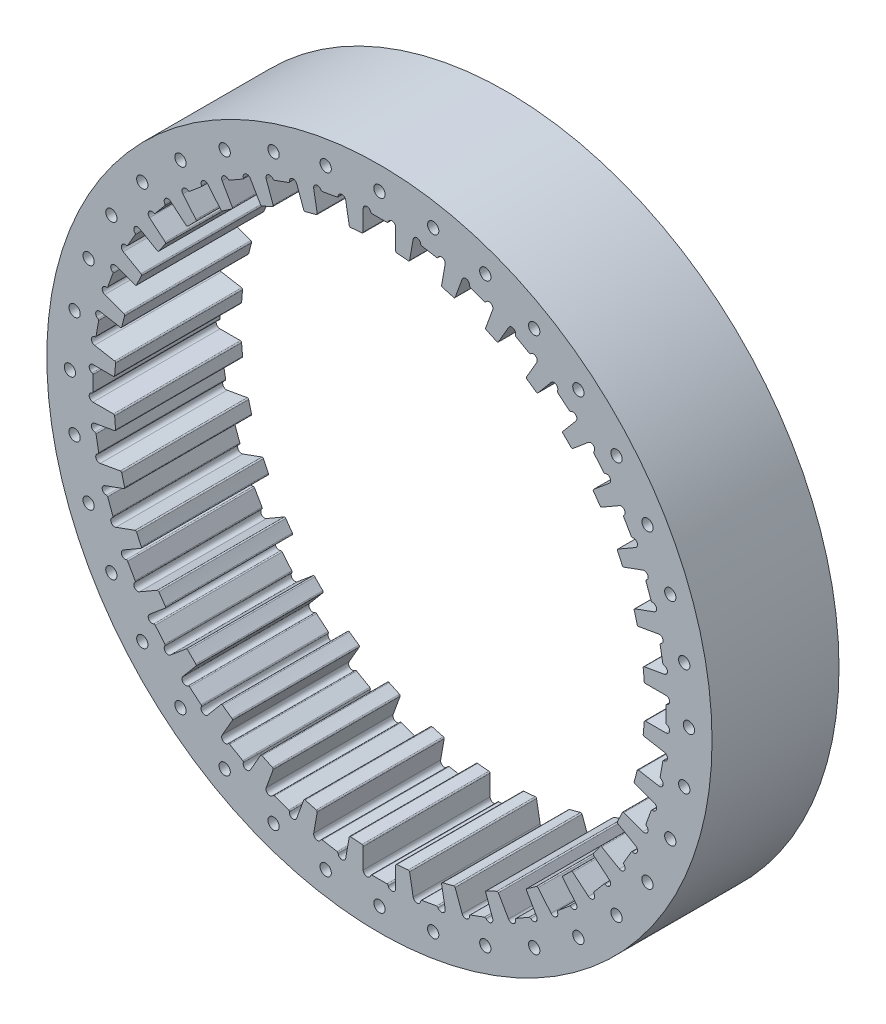
SolidWorks part; units mm, degrees
material "ABS"
ref_plane "Front Plane" through (0, 0, 0) normal (0, 0, 1) x (1, 0, 0)
ref_plane "Top Plane" through (0, 0, 0) normal (0, 1, 0) x (1, 0, 0)
ref_plane "Right Plane" through (0, 0, 0) normal (1, 0, 0) x (0, 0, -1)
ref_axis "Axis1" through (0, 0, -101.69) along (0, 0, 1)
sketch "Sketch1" plane through (0, 0, 0) normal (0, 0, 1) x (1, 0, 0)
  line L0 (0, 0) -> (50000, 0) construction
  line L1 (0, 0) -> (0, 50000) construction
  circle A0 centre (0, 0) radius 66.548
  circle A1 centre (0, 0) radius 53.086
  dimension "D1" = 133.096
  dimension "D2" = 106.172
extrude "Boss-Extrude1" add sketch "Sketch1" against normal blind 25.4
sketch "Sketch2" plane through (0, 0, 0) normal (0, 0, 1) x (1, 0, 0)
  line L0 (0, 0) -> (50000, 0) construction
  line L1 (0, 0) -> (0, 50000) construction
  circle A0 centre (0, 61.9252) radius 1.1303
  dimension "D1" = 2.2606
  dimension "D2" = 61.9252
extrude "Cut-Extrude1" cut sketch "Sketch2" against normal up to surface (25.4 mm away) up to face at (53.086, 0, -25.4)
pattern_circular "CirPattern1" count 36 over 360 about axis through (0, 0, -101.69) along (0, 0, 1) of "Cut-Extrude1"
sketch "Sketch3" plane through (0, 0, 0) normal (0, 0, 1) x (1, 0, 0)
  line L0 (0, 0) -> (50000, 0) construction
  line L1 (0, 0) -> (0, 50000) construction
  line L2 (57.3024, 1.5055) -> (57.3024, -1.5055)
  line L3 (57.3024, -3.2512) -> (53.2247, -3.2512)
  line L4 (57.3024, 3.2512) -> (53.2247, 3.2512)
  circle A0 centre (0, 0) radius 53.086 construction
  circle A2 centre (0, 0) radius 53.086 construction
  arc A3 (57.3024, -1.5055) -> (57.4929, -1.7514) centre (57.5564, -1.5055) ccw
  arc A4 (57.4929, -1.7514) -> (57.3024, -3.2512) centre (57.3024, -2.4892) cw
  arc A5 (53.2247, -3.2512) -> (52.9713, -3.4885) centre (53.2247, -3.5052) ccw
  arc A6 (53.2247, 3.2512) -> (52.9713, 3.4885) centre (53.2247, 3.5052) cw
  arc A7 (57.4929, 1.7514) -> (57.3024, 3.2512) centre (57.3024, 2.4892) ccw
  arc A8 (57.3024, 1.5055) -> (57.4929, 1.7514) centre (57.5564, 1.5055) cw
  arc A9 (52.9713, 3.4885) -> (52.9713, -3.4885) centre (0, 0) cw
  point P27 (57.3024, 0)
  dimension "D1" = 0.254
  dimension "D2" = 0.762
  dimension "D3" = 57.3024
  dimension "D4" = 3.2512
extrude "Cut-Extrude2" cut sketch "Sketch3" against normal blind 25.4 contours A6 A9 A5 L3 A4 A3 L2 A8 A7 L4 region at (55.3285, 0, 0)
pattern_circular "CirPattern2" count 36 over 360 about axis through (0, 0, -101.69) along (0, 0, 1) of "Cut-Extrude2"
sketch "Sketch4" plane through (0, 0, 0) normal (0, 0, 1) x (1, 0, 0)
  line L0 (0, 0) -> (-50000, 0) construction
  line L1 (0, 0) -> (0, 50000) construction
  line L2 (-1.5055, 57.3024) -> (1.5055, 57.3024) construction
  line L3 (-2.921, 57.3024) -> (2.921, 57.3024)
  line L4 (-3.175, 57.0484) -> (-3.175, 51.2064)
  line L5 (-2.921, 50.9524) -> (2.921, 50.9524)
  line L6 (3.175, 57.0484) -> (3.175, 51.2064)
  line L7 (7.0738, 56.9391) -> (12.8271, 55.9246)
  line L8 (6.7796, 56.733) -> (5.7651, 50.9798)
  line L9 (5.9712, 50.6855) -> (11.7244, 49.6711)
  line L10 (13.0331, 55.6304) -> (12.0187, 49.8771)
  line L11 (16.8537, 54.8457) -> (22.3434, 52.8476)
  line L12 (16.5282, 54.6939) -> (14.5301, 49.2042)
  line L13 (14.6819, 48.8786) -> (20.1716, 46.8806)
  line L14 (22.4952, 52.522) -> (20.4971, 47.0324)
  line L15 (26.1215, 51.0858) -> (31.1809, 48.1648)
  line L16 (25.7746, 50.9929) -> (22.8536, 45.9335)
  line L17 (22.9465, 45.5866) -> (28.0059, 42.6656)
  line L18 (31.2738, 47.8179) -> (28.3528, 42.7585)
  line L19 (34.5957, 45.7738) -> (39.0709, 42.0186)
  line L20 (34.2378, 45.7425) -> (30.4826, 41.2672)
  line L21 (30.514, 40.9094) -> (34.9892, 37.1542)
  line L22 (39.1022, 41.6608) -> (35.347, 37.1855)
  line L23 (42.0186, 39.0709) -> (45.7738, 34.5957)
  line L24 (41.6608, 39.1022) -> (37.1855, 35.347)
  line L25 (37.1542, 34.9892) -> (40.9094, 30.514)
  line L26 (45.7425, 34.2378) -> (41.2672, 30.4826)
  line L27 (48.1648, 31.1809) -> (51.0858, 26.1215)
  line L28 (47.8179, 31.2738) -> (42.7585, 28.3528)
  line L29 (42.6656, 28.0059) -> (45.5866, 22.9465)
  line L30 (50.9929, 25.7746) -> (45.9335, 22.8536)
  line L31 (52.8476, 22.3434) -> (54.8457, 16.8537)
  line L32 (52.522, 22.4952) -> (47.0324, 20.4971)
  line L33 (46.8806, 20.1716) -> (48.8786, 14.6819)
  line L34 (54.6939, 16.5282) -> (49.2042, 14.5301)
  line L35 (55.9246, 12.8271) -> (56.9391, 7.0738)
  line L36 (55.6304, 13.0331) -> (49.8771, 12.0187)
  line L37 (49.6711, 11.7244) -> (50.6855, 5.9712)
  line L38 (56.733, 6.7796) -> (50.9798, 5.7651)
  line L39 (57.3024, 2.921) -> (57.3024, -2.921)
  line L40 (57.0484, 3.175) -> (51.2064, 3.175)
  line L41 (50.9524, 2.921) -> (50.9524, -2.921)
  line L42 (57.0484, -3.175) -> (51.2064, -3.175)
  line L43 (56.9391, -7.0738) -> (55.9246, -12.8271)
  line L44 (56.733, -6.7796) -> (50.9798, -5.7651)
  line L45 (50.6855, -5.9712) -> (49.6711, -11.7244)
  line L46 (55.6304, -13.0331) -> (49.8771, -12.0187)
  line L47 (54.8457, -16.8537) -> (52.8476, -22.3434)
  line L48 (54.6939, -16.5282) -> (49.2042, -14.5301)
  line L49 (48.8786, -14.6819) -> (46.8806, -20.1716)
  line L50 (52.522, -22.4952) -> (47.0324, -20.4971)
  line L51 (51.0858, -26.1215) -> (48.1648, -31.1809)
  line L52 (50.9929, -25.7746) -> (45.9335, -22.8536)
  line L53 (45.5866, -22.9465) -> (42.6656, -28.0059)
  line L54 (47.8179, -31.2738) -> (42.7585, -28.3528)
  line L55 (45.7738, -34.5957) -> (42.0186, -39.0709)
  line L56 (45.7425, -34.2378) -> (41.2672, -30.4826)
  line L57 (40.9094, -30.514) -> (37.1542, -34.9892)
  line L58 (41.6608, -39.1022) -> (37.1855, -35.347)
  line L59 (39.0709, -42.0186) -> (34.5957, -45.7738)
  line L60 (39.1022, -41.6608) -> (35.347, -37.1855)
  line L61 (34.9892, -37.1542) -> (30.514, -40.9094)
  line L62 (34.2378, -45.7425) -> (30.4826, -41.2672)
  line L63 (31.1809, -48.1648) -> (26.1215, -51.0858)
  line L64 (31.2738, -47.8179) -> (28.3528, -42.7585)
  line L65 (28.0059, -42.6656) -> (22.9465, -45.5866)
  line L66 (25.7746, -50.9929) -> (22.8536, -45.9335)
  line L67 (22.3434, -52.8476) -> (16.8537, -54.8457)
  line L68 (22.4952, -52.522) -> (20.4971, -47.0324)
  line L69 (20.1716, -46.8806) -> (14.6819, -48.8786)
  line L70 (16.5282, -54.6939) -> (14.5301, -49.2042)
  line L71 (12.8271, -55.9246) -> (7.0738, -56.9391)
  line L72 (13.0331, -55.6304) -> (12.0187, -49.8771)
  line L73 (11.7244, -49.6711) -> (5.9712, -50.6855)
  line L74 (6.7796, -56.733) -> (5.7651, -50.9798)
  line L75 (2.921, -57.3024) -> (-2.921, -57.3024)
  line L76 (3.175, -57.0484) -> (3.175, -51.2064)
  line L77 (2.921, -50.9524) -> (-2.921, -50.9524)
  line L78 (-3.175, -57.0484) -> (-3.175, -51.2064)
  line L79 (-7.0738, -56.9391) -> (-12.8271, -55.9246)
  line L80 (-6.7796, -56.733) -> (-5.7651, -50.9798)
  line L81 (-5.9712, -50.6855) -> (-11.7244, -49.6711)
  line L82 (-13.0331, -55.6304) -> (-12.0187, -49.8771)
  line L83 (-16.8537, -54.8457) -> (-22.3434, -52.8476)
  line L84 (-16.5282, -54.6939) -> (-14.5301, -49.2042)
  line L85 (-14.6819, -48.8786) -> (-20.1716, -46.8806)
  line L86 (-22.4952, -52.522) -> (-20.4971, -47.0324)
  line L87 (-26.1215, -51.0858) -> (-31.1809, -48.1648)
  line L88 (-25.7746, -50.9929) -> (-22.8536, -45.9335)
  line L89 (-22.9465, -45.5866) -> (-28.0059, -42.6656)
  line L90 (-31.2738, -47.8179) -> (-28.3528, -42.7585)
  line L91 (-34.5957, -45.7738) -> (-39.0709, -42.0186)
  line L92 (-34.2378, -45.7425) -> (-30.4826, -41.2672)
  line L93 (-30.514, -40.9094) -> (-34.9892, -37.1542)
  line L94 (-39.1022, -41.6608) -> (-35.347, -37.1855)
  line L95 (-42.0186, -39.0709) -> (-45.7738, -34.5957)
  line L96 (-41.6608, -39.1022) -> (-37.1855, -35.347)
  line L97 (-37.1542, -34.9892) -> (-40.9094, -30.514)
  line L98 (-45.7425, -34.2378) -> (-41.2672, -30.4826)
  line L99 (-48.1648, -31.1809) -> (-51.0858, -26.1215)
  line L100 (-47.8179, -31.2738) -> (-42.7585, -28.3528)
  line L101 (-42.6656, -28.0059) -> (-45.5866, -22.9465)
  line L102 (-50.9929, -25.7746) -> (-45.9335, -22.8536)
  line L103 (-52.8476, -22.3434) -> (-54.8457, -16.8537)
  line L104 (-52.522, -22.4952) -> (-47.0324, -20.4971)
  line L105 (-46.8806, -20.1716) -> (-48.8786, -14.6819)
  line L106 (-54.6939, -16.5282) -> (-49.2042, -14.5301)
  line L107 (-55.9246, -12.8271) -> (-56.9391, -7.0738)
  line L108 (-55.6304, -13.0331) -> (-49.8771, -12.0187)
  line L109 (-49.6711, -11.7244) -> (-50.6855, -5.9712)
  line L110 (-56.733, -6.7796) -> (-50.9798, -5.7651)
  line L111 (-57.3024, -2.921) -> (-57.3024, 2.921)
  line L112 (-57.0484, -3.175) -> (-51.2064, -3.175)
  line L113 (-50.9524, -2.921) -> (-50.9524, 2.921)
  line L114 (-57.0484, 3.175) -> (-51.2064, 3.175)
  line L115 (-56.9391, 7.0738) -> (-55.9246, 12.8271)
  line L116 (-56.733, 6.7796) -> (-50.9798, 5.7651)
  line L117 (-50.6855, 5.9712) -> (-49.6711, 11.7244)
  line L118 (-55.6304, 13.0331) -> (-49.8771, 12.0187)
  line L119 (-54.8457, 16.8537) -> (-52.8476, 22.3434)
  line L120 (-54.6939, 16.5282) -> (-49.2042, 14.5301)
  line L121 (-48.8786, 14.6819) -> (-46.8806, 20.1716)
  line L122 (-52.522, 22.4952) -> (-47.0324, 20.4971)
  line L123 (-51.0858, 26.1215) -> (-48.1648, 31.1809)
  line L124 (-50.9929, 25.7746) -> (-45.9335, 22.8536)
  line L125 (-45.5866, 22.9465) -> (-42.6656, 28.0059)
  line L126 (-47.8179, 31.2738) -> (-42.7585, 28.3528)
  line L127 (-45.7738, 34.5957) -> (-42.0186, 39.0709)
  line L128 (-45.7425, 34.2378) -> (-41.2672, 30.4826)
  line L129 (-40.9094, 30.514) -> (-37.1542, 34.9892)
  line L130 (-41.6608, 39.1022) -> (-37.1855, 35.347)
  line L131 (-39.0709, 42.0186) -> (-34.5957, 45.7738)
  line L132 (-39.1022, 41.6608) -> (-35.347, 37.1855)
  line L133 (-34.9892, 37.1542) -> (-30.514, 40.9094)
  line L134 (-34.2378, 45.7425) -> (-30.4826, 41.2672)
  line L135 (-31.1809, 48.1648) -> (-26.1215, 51.0858)
  line L136 (-31.2738, 47.8179) -> (-28.3528, 42.7585)
  line L137 (-28.0059, 42.6656) -> (-22.9465, 45.5866)
  line L138 (-25.7746, 50.9929) -> (-22.8536, 45.9335)
  line L139 (-22.3434, 52.8476) -> (-16.8537, 54.8457)
  line L140 (-22.4952, 52.522) -> (-20.4971, 47.0324)
  line L141 (-20.1716, 46.8806) -> (-14.6819, 48.8786)
  line L142 (-16.5282, 54.6939) -> (-14.5301, 49.2042)
  line L143 (-12.8271, 55.9246) -> (-7.0738, 56.9391)
  line L144 (-13.0331, 55.6304) -> (-12.0187, 49.8771)
  line L145 (-11.7244, 49.6711) -> (-5.9712, 50.6855)
  line L146 (-6.7796, 56.733) -> (-5.7651, 50.9798)
  arc A0 (-2.921, 50.9524) -> (-3.175, 51.2064) centre (-2.921, 51.2064) cw
  arc A1 (3.175, 51.2064) -> (2.921, 50.9524) centre (2.921, 51.2064) cw
  arc A2 (3.175, 57.0484) -> (2.921, 57.3024) centre (2.921, 57.0484) ccw
  arc A3 (-3.175, 57.0484) -> (-2.921, 57.3024) centre (-2.921, 57.0484) cw
  arc A4 (5.9712, 50.6855) -> (5.7651, 50.9798) centre (6.0153, 50.9357) cw
  arc A5 (12.0187, 49.8771) -> (11.7244, 49.6711) centre (11.7685, 49.9212) cw
  arc A6 (13.0331, 55.6304) -> (12.8271, 55.9246) centre (12.783, 55.6745) ccw
  arc A7 (6.7796, 56.733) -> (7.0738, 56.9391) centre (7.0297, 56.6889) cw
  arc A8 (14.6819, 48.8786) -> (14.5301, 49.2042) centre (14.7688, 49.1173) cw
  arc A9 (20.4971, 47.0324) -> (20.1716, 46.8806) centre (20.2585, 47.1192) cw
  arc A10 (22.4952, 52.522) -> (22.3434, 52.8476) centre (22.2565, 52.6089) ccw
  arc A11 (16.5282, 54.6939) -> (16.8537, 54.8457) centre (16.7669, 54.607) cw
  arc A12 (22.9465, 45.5866) -> (22.8536, 45.9335) centre (23.0735, 45.8065) cw
  arc A13 (28.3528, 42.7585) -> (28.0059, 42.6656) centre (28.1329, 42.8855) cw
  arc A14 (31.2738, 47.8179) -> (31.1809, 48.1648) centre (31.0539, 47.9449) ccw
  arc A15 (25.7746, 50.9929) -> (26.1215, 51.0858) centre (25.9945, 50.8659) cw
  arc A16 (30.514, 40.9094) -> (30.4826, 41.2672) centre (30.6772, 41.104) cw
  arc A17 (35.347, 37.1855) -> (34.9892, 37.1542) centre (35.1525, 37.3488) cw
  arc A18 (39.1022, 41.6608) -> (39.0709, 42.0186) centre (38.9076, 41.824) ccw
  arc A19 (34.2378, 45.7425) -> (34.5957, 45.7738) centre (34.4324, 45.5792) cw
  arc A20 (37.1542, 34.9892) -> (37.1855, 35.347) centre (37.3488, 35.1525) cw
  arc A21 (41.2672, 30.4826) -> (40.9094, 30.514) centre (41.104, 30.6772) cw
  arc A22 (45.7425, 34.2378) -> (45.7738, 34.5957) centre (45.5792, 34.4324) ccw
  arc A23 (41.6608, 39.1022) -> (42.0186, 39.0709) centre (41.824, 38.9076) cw
  arc A24 (42.6656, 28.0059) -> (42.7585, 28.3528) centre (42.8855, 28.1329) cw
  arc A25 (45.9335, 22.8536) -> (45.5866, 22.9465) centre (45.8065, 23.0735) cw
  arc A26 (50.9929, 25.7746) -> (51.0858, 26.1215) centre (50.8659, 25.9945) ccw
  arc A27 (47.8179, 31.2738) -> (48.1648, 31.1809) centre (47.9449, 31.0539) cw
  arc A28 (46.8806, 20.1716) -> (47.0324, 20.4971) centre (47.1192, 20.2585) cw
  arc A29 (49.2042, 14.5301) -> (48.8786, 14.6819) centre (49.1173, 14.7688) cw
  arc A30 (54.6939, 16.5282) -> (54.8457, 16.8537) centre (54.607, 16.7669) ccw
  arc A31 (52.522, 22.4952) -> (52.8476, 22.3434) centre (52.6089, 22.2565) cw
  arc A32 (49.6711, 11.7244) -> (49.8771, 12.0187) centre (49.9212, 11.7685) cw
  arc A33 (50.9798, 5.7651) -> (50.6855, 5.9712) centre (50.9357, 6.0153) cw
  arc A34 (56.733, 6.7796) -> (56.9391, 7.0738) centre (56.6889, 7.0297) ccw
  arc A35 (55.6304, 13.0331) -> (55.9246, 12.8271) centre (55.6745, 12.783) cw
  arc A36 (50.9524, 2.921) -> (51.2064, 3.175) centre (51.2064, 2.921) cw
  arc A37 (51.2064, -3.175) -> (50.9524, -2.921) centre (51.2064, -2.921) cw
  arc A38 (57.0484, -3.175) -> (57.3024, -2.921) centre (57.0484, -2.921) ccw
  arc A39 (57.0484, 3.175) -> (57.3024, 2.921) centre (57.0484, 2.921) cw
  arc A40 (50.6855, -5.9712) -> (50.9798, -5.7651) centre (50.9357, -6.0153) cw
  arc A41 (49.8771, -12.0187) -> (49.6711, -11.7244) centre (49.9212, -11.7685) cw
  arc A42 (55.6304, -13.0331) -> (55.9246, -12.8271) centre (55.6745, -12.783) ccw
  arc A43 (56.733, -6.7796) -> (56.9391, -7.0738) centre (56.6889, -7.0297) cw
  arc A44 (48.8786, -14.6819) -> (49.2042, -14.5301) centre (49.1173, -14.7688) cw
  arc A45 (47.0324, -20.4971) -> (46.8806, -20.1716) centre (47.1192, -20.2585) cw
  arc A46 (52.522, -22.4952) -> (52.8476, -22.3434) centre (52.6089, -22.2565) ccw
  arc A47 (54.6939, -16.5282) -> (54.8457, -16.8537) centre (54.607, -16.7669) cw
  arc A48 (45.5866, -22.9465) -> (45.9335, -22.8536) centre (45.8065, -23.0735) cw
  arc A49 (42.7585, -28.3528) -> (42.6656, -28.0059) centre (42.8855, -28.1329) cw
  arc A50 (47.8179, -31.2738) -> (48.1648, -31.1809) centre (47.9449, -31.0539) ccw
  arc A51 (50.9929, -25.7746) -> (51.0858, -26.1215) centre (50.8659, -25.9945) cw
  arc A52 (40.9094, -30.514) -> (41.2672, -30.4826) centre (41.104, -30.6772) cw
  arc A53 (37.1855, -35.347) -> (37.1542, -34.9892) centre (37.3488, -35.1525) cw
  arc A54 (41.6608, -39.1022) -> (42.0186, -39.0709) centre (41.824, -38.9076) ccw
  arc A55 (45.7425, -34.2378) -> (45.7738, -34.5957) centre (45.5792, -34.4324) cw
  arc A56 (34.9892, -37.1542) -> (35.347, -37.1855) centre (35.1525, -37.3488) cw
  arc A57 (30.4826, -41.2672) -> (30.514, -40.9094) centre (30.6772, -41.104) cw
  arc A58 (34.2378, -45.7425) -> (34.5957, -45.7738) centre (34.4324, -45.5792) ccw
  arc A59 (39.1022, -41.6608) -> (39.0709, -42.0186) centre (38.9076, -41.824) cw
  arc A60 (28.0059, -42.6656) -> (28.3528, -42.7585) centre (28.1329, -42.8855) cw
  arc A61 (22.8536, -45.9335) -> (22.9465, -45.5866) centre (23.0735, -45.8065) cw
  arc A62 (25.7746, -50.9929) -> (26.1215, -51.0858) centre (25.9945, -50.8659) ccw
  arc A63 (31.2738, -47.8179) -> (31.1809, -48.1648) centre (31.0539, -47.9449) cw
  arc A64 (20.1716, -46.8806) -> (20.4971, -47.0324) centre (20.2585, -47.1192) cw
  arc A65 (14.5301, -49.2042) -> (14.6819, -48.8786) centre (14.7688, -49.1173) cw
  arc A66 (16.5282, -54.6939) -> (16.8537, -54.8457) centre (16.7669, -54.607) ccw
  arc A67 (22.4952, -52.522) -> (22.3434, -52.8476) centre (22.2565, -52.6089) cw
  arc A68 (11.7244, -49.6711) -> (12.0187, -49.8771) centre (11.7685, -49.9212) cw
  arc A69 (5.7651, -50.9798) -> (5.9712, -50.6855) centre (6.0153, -50.9357) cw
  arc A70 (6.7796, -56.733) -> (7.0738, -56.9391) centre (7.0297, -56.6889) ccw
  arc A71 (13.0331, -55.6304) -> (12.8271, -55.9246) centre (12.783, -55.6745) cw
  arc A72 (2.921, -50.9524) -> (3.175, -51.2064) centre (2.921, -51.2064) cw
  arc A73 (-3.175, -51.2064) -> (-2.921, -50.9524) centre (-2.921, -51.2064) cw
  arc A74 (-3.175, -57.0484) -> (-2.921, -57.3024) centre (-2.921, -57.0484) ccw
  arc A75 (3.175, -57.0484) -> (2.921, -57.3024) centre (2.921, -57.0484) cw
  arc A76 (-5.9712, -50.6855) -> (-5.7651, -50.9798) centre (-6.0153, -50.9357) cw
  arc A77 (-12.0187, -49.8771) -> (-11.7244, -49.6711) centre (-11.7685, -49.9212) cw
  arc A78 (-13.0331, -55.6304) -> (-12.8271, -55.9246) centre (-12.783, -55.6745) ccw
  arc A79 (-6.7796, -56.733) -> (-7.0738, -56.9391) centre (-7.0297, -56.6889) cw
  arc A80 (-14.6819, -48.8786) -> (-14.5301, -49.2042) centre (-14.7688, -49.1173) cw
  arc A81 (-20.4971, -47.0324) -> (-20.1716, -46.8806) centre (-20.2585, -47.1192) cw
  arc A82 (-22.4952, -52.522) -> (-22.3434, -52.8476) centre (-22.2565, -52.6089) ccw
  arc A83 (-16.5282, -54.6939) -> (-16.8537, -54.8457) centre (-16.7669, -54.607) cw
  arc A84 (-22.9465, -45.5866) -> (-22.8536, -45.9335) centre (-23.0735, -45.8065) cw
  arc A85 (-28.3528, -42.7585) -> (-28.0059, -42.6656) centre (-28.1329, -42.8855) cw
  arc A86 (-31.2738, -47.8179) -> (-31.1809, -48.1648) centre (-31.0539, -47.9449) ccw
  arc A87 (-25.7746, -50.9929) -> (-26.1215, -51.0858) centre (-25.9945, -50.8659) cw
  arc A88 (-30.514, -40.9094) -> (-30.4826, -41.2672) centre (-30.6772, -41.104) cw
  arc A89 (-35.347, -37.1855) -> (-34.9892, -37.1542) centre (-35.1525, -37.3488) cw
  arc A90 (-39.1022, -41.6608) -> (-39.0709, -42.0186) centre (-38.9076, -41.824) ccw
  arc A91 (-34.2378, -45.7425) -> (-34.5957, -45.7738) centre (-34.4324, -45.5792) cw
  arc A92 (-37.1542, -34.9892) -> (-37.1855, -35.347) centre (-37.3488, -35.1525) cw
  arc A93 (-41.2672, -30.4826) -> (-40.9094, -30.514) centre (-41.104, -30.6772) cw
  arc A94 (-45.7425, -34.2378) -> (-45.7738, -34.5957) centre (-45.5792, -34.4324) ccw
  arc A95 (-41.6608, -39.1022) -> (-42.0186, -39.0709) centre (-41.824, -38.9076) cw
  arc A96 (-42.6656, -28.0059) -> (-42.7585, -28.3528) centre (-42.8855, -28.1329) cw
  arc A97 (-45.9335, -22.8536) -> (-45.5866, -22.9465) centre (-45.8065, -23.0735) cw
  arc A98 (-50.9929, -25.7746) -> (-51.0858, -26.1215) centre (-50.8659, -25.9945) ccw
  arc A99 (-47.8179, -31.2738) -> (-48.1648, -31.1809) centre (-47.9449, -31.0539) cw
  arc A100 (-46.8806, -20.1716) -> (-47.0324, -20.4971) centre (-47.1192, -20.2585) cw
  arc A101 (-49.2042, -14.5301) -> (-48.8786, -14.6819) centre (-49.1173, -14.7688) cw
  arc A102 (-54.6939, -16.5282) -> (-54.8457, -16.8537) centre (-54.607, -16.7669) ccw
  arc A103 (-52.522, -22.4952) -> (-52.8476, -22.3434) centre (-52.6089, -22.2565) cw
  arc A104 (-49.6711, -11.7244) -> (-49.8771, -12.0187) centre (-49.9212, -11.7685) cw
  arc A105 (-50.9798, -5.7651) -> (-50.6855, -5.9712) centre (-50.9357, -6.0153) cw
  arc A106 (-56.733, -6.7796) -> (-56.9391, -7.0738) centre (-56.6889, -7.0297) ccw
  arc A107 (-55.6304, -13.0331) -> (-55.9246, -12.8271) centre (-55.6745, -12.783) cw
  arc A108 (-50.9524, -2.921) -> (-51.2064, -3.175) centre (-51.2064, -2.921) cw
  arc A109 (-51.2064, 3.175) -> (-50.9524, 2.921) centre (-51.2064, 2.921) cw
  arc A110 (-57.0484, 3.175) -> (-57.3024, 2.921) centre (-57.0484, 2.921) ccw
  arc A111 (-57.0484, -3.175) -> (-57.3024, -2.921) centre (-57.0484, -2.921) cw
  arc A112 (-50.6855, 5.9712) -> (-50.9798, 5.7651) centre (-50.9357, 6.0153) cw
  arc A113 (-49.8771, 12.0187) -> (-49.6711, 11.7244) centre (-49.9212, 11.7685) cw
  arc A114 (-55.6304, 13.0331) -> (-55.9246, 12.8271) centre (-55.6745, 12.783) ccw
  arc A115 (-56.733, 6.7796) -> (-56.9391, 7.0738) centre (-56.6889, 7.0297) cw
  arc A116 (-48.8786, 14.6819) -> (-49.2042, 14.5301) centre (-49.1173, 14.7688) cw
  arc A117 (-47.0324, 20.4971) -> (-46.8806, 20.1716) centre (-47.1192, 20.2585) cw
  arc A118 (-52.522, 22.4952) -> (-52.8476, 22.3434) centre (-52.6089, 22.2565) ccw
  arc A119 (-54.6939, 16.5282) -> (-54.8457, 16.8537) centre (-54.607, 16.7669) cw
  arc A120 (-45.5866, 22.9465) -> (-45.9335, 22.8536) centre (-45.8065, 23.0735) cw
  arc A121 (-42.7585, 28.3528) -> (-42.6656, 28.0059) centre (-42.8855, 28.1329) cw
  arc A122 (-47.8179, 31.2738) -> (-48.1648, 31.1809) centre (-47.9449, 31.0539) ccw
  arc A123 (-50.9929, 25.7746) -> (-51.0858, 26.1215) centre (-50.8659, 25.9945) cw
  arc A124 (-40.9094, 30.514) -> (-41.2672, 30.4826) centre (-41.104, 30.6772) cw
  arc A125 (-37.1855, 35.347) -> (-37.1542, 34.9892) centre (-37.3488, 35.1525) cw
  arc A126 (-41.6608, 39.1022) -> (-42.0186, 39.0709) centre (-41.824, 38.9076) ccw
  arc A127 (-45.7425, 34.2378) -> (-45.7738, 34.5957) centre (-45.5792, 34.4324) cw
  arc A128 (-34.9892, 37.1542) -> (-35.347, 37.1855) centre (-35.1525, 37.3488) cw
  arc A129 (-30.4826, 41.2672) -> (-30.514, 40.9094) centre (-30.6772, 41.104) cw
  arc A130 (-34.2378, 45.7425) -> (-34.5957, 45.7738) centre (-34.4324, 45.5792) ccw
  arc A131 (-39.1022, 41.6608) -> (-39.0709, 42.0186) centre (-38.9076, 41.824) cw
  arc A132 (-28.0059, 42.6656) -> (-28.3528, 42.7585) centre (-28.1329, 42.8855) cw
  arc A133 (-22.8536, 45.9335) -> (-22.9465, 45.5866) centre (-23.0735, 45.8065) cw
  arc A134 (-25.7746, 50.9929) -> (-26.1215, 51.0858) centre (-25.9945, 50.8659) ccw
  arc A135 (-31.2738, 47.8179) -> (-31.1809, 48.1648) centre (-31.0539, 47.9449) cw
  arc A136 (-20.1716, 46.8806) -> (-20.4971, 47.0324) centre (-20.2585, 47.1192) cw
  arc A137 (-14.5301, 49.2042) -> (-14.6819, 48.8786) centre (-14.7688, 49.1173) cw
  arc A138 (-16.5282, 54.6939) -> (-16.8537, 54.8457) centre (-16.7669, 54.607) ccw
  arc A139 (-22.4952, 52.522) -> (-22.3434, 52.8476) centre (-22.2565, 52.6089) cw
  arc A140 (-11.7244, 49.6711) -> (-12.0187, 49.8771) centre (-11.7685, 49.9212) cw
  arc A141 (-5.7651, 50.9798) -> (-5.9712, 50.6855) centre (-6.0153, 50.9357) cw
  arc A142 (-6.7796, 56.733) -> (-7.0738, 56.9391) centre (-7.0297, 56.6889) ccw
  arc A143 (-13.0331, 55.6304) -> (-12.8271, 55.9246) centre (-12.783, 55.6745) cw
  point P12 (-3.175, 50.9524)
  point P17 (3.175, 57.3024)
  point P20 (-3.175, 57.3024)
  point P445 (0, 0)
  dimension "D3" = 0.254
  dimension "D1" = 6.35
  dimension "D2" = 6.35
